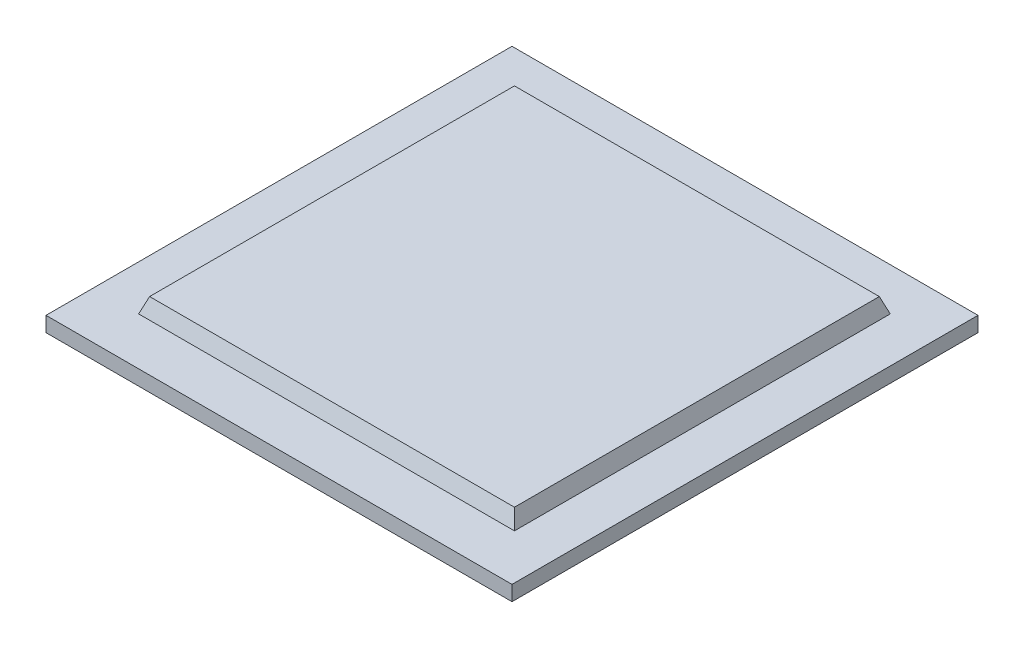
SolidWorks part; units mm, degrees
ref_plane "Front Plane" through (0, 0, 0) normal (0, 0, 1) x (1, 0, 0)
ref_plane "Top Plane" through (0, 0, 0) normal (0, 1, 0) x (1, 0, 0)
ref_plane "Right Plane" through (0, 0, 0) normal (1, 0, 0) x (0, 0, -1)
sketch "Sketch8" plane through (0, 0, 0) normal (0, 1, 0) x (1, 0, 0)
  line L1 (-15.5, 15.5) -> (15.5, 15.5)
  line L2 (-15.5, 15.5) -> (-15.5, -15.5)
  line L3 (-15.5, -15.5) -> (15.5, -15.5)
  line L4 (15.5, 15.5) -> (15.5, -15.5)
extrude "Boss-Extrude4" add sketch "Sketch8" along normal blind 1 separate body
sketch "Sketch16" plane through (0, 1, 0) normal (0, 1, 0) x (1, 0, 0)
  line L1 (-12.5, 12.663) -> (12.5, 12.663)
  line L2 (-12.5, 12.663) -> (-12.5, -12.337)
  line L3 (-12.5, -12.337) -> (12.5, -12.337)
  line L4 (12.5, 12.663) -> (12.5, -12.337)
extrude "Boss-Extrude11" add sketch "Sketch16" along normal blind 1 draft 20
ref_plane "Plane1" through (0, 0, 0) normal (-0.7071, 0, 0.7071) x (0.7071, 0, 0.7071)
ref_plane "Plane2" through (0, 0, 0) normal (0.7071, 0, 0.7071) x (0.7071, 0, -0.7071)
ref_axis "Axis1" through (0, -1.6461, 0) along (0, 1, 0)
